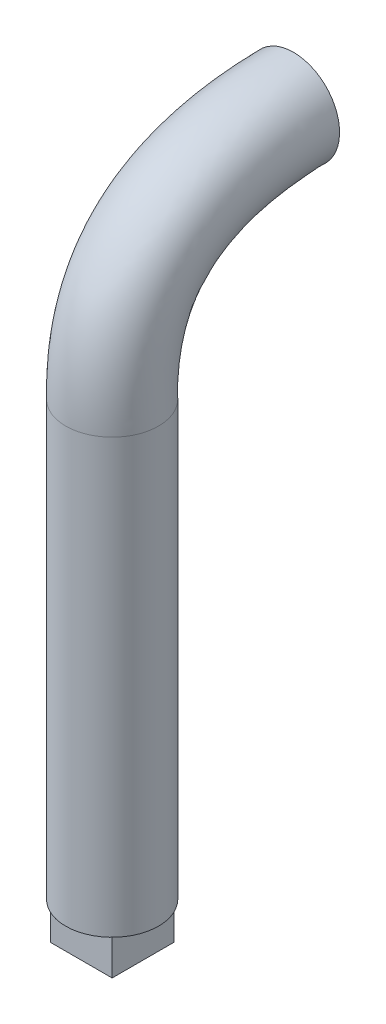
SolidWorks part; units mm, degrees
ref_plane "Front Plane" through (0, 0, 0) normal (0, 0, 1) x (1, 0, 0)
ref_plane "Top Plane" through (0, 0, 0) normal (0, 1, 0) x (1, 0, 0)
ref_plane "Right Plane" through (0, 0, 0) normal (1, 0, 0) x (0, 0, -1)
sketch "Sketch1" plane through (0, 0, 0) normal (0, 1, 0) x (1, 0, 0)
  circle A0 centre (0, 0) radius 7.5
extrude "Boss-Extrude1" add sketch "Sketch1" along normal blind 70
sketch "Sketch2" plane through (0, 0, 0) normal (0, -1, 0) x (1, 0, 0)
  line L1 (-5, 5) -> (5, 5)
  line L2 (-5, 5) -> (-5, -5)
  line L3 (-5, -5) -> (5, -5)
  line L4 (5, 5) -> (5, -5)
  line L5 (-5, 5) -> (5, -5) construction
  line L6 (-5, -5) -> (5, 5) construction
  point P0 (0, 0)
extrude "Boss-Extrude2" add sketch "Sketch2" along normal blind 6
sketch "Sketch3" plane through (0, 0, 0) normal (1, 0, 0) x (0, 0, -1)
  line L0 (7.5, 70) -> (-7.5, 70) construction
  spline S0 degree 2 poles (0, 70) (-0.6718, 95.8831) (29.2595, 96.4198) knots 0 0 0 1 1 1
sketch "Sketch4" plane through (0, 70, 0) normal (0, 1, 0) x (1, 0, 0)
  circle A0 centre (0, 0) radius 7.5
sweep "Sweep1" add profiles "Sketch4" path "Sketch3"
